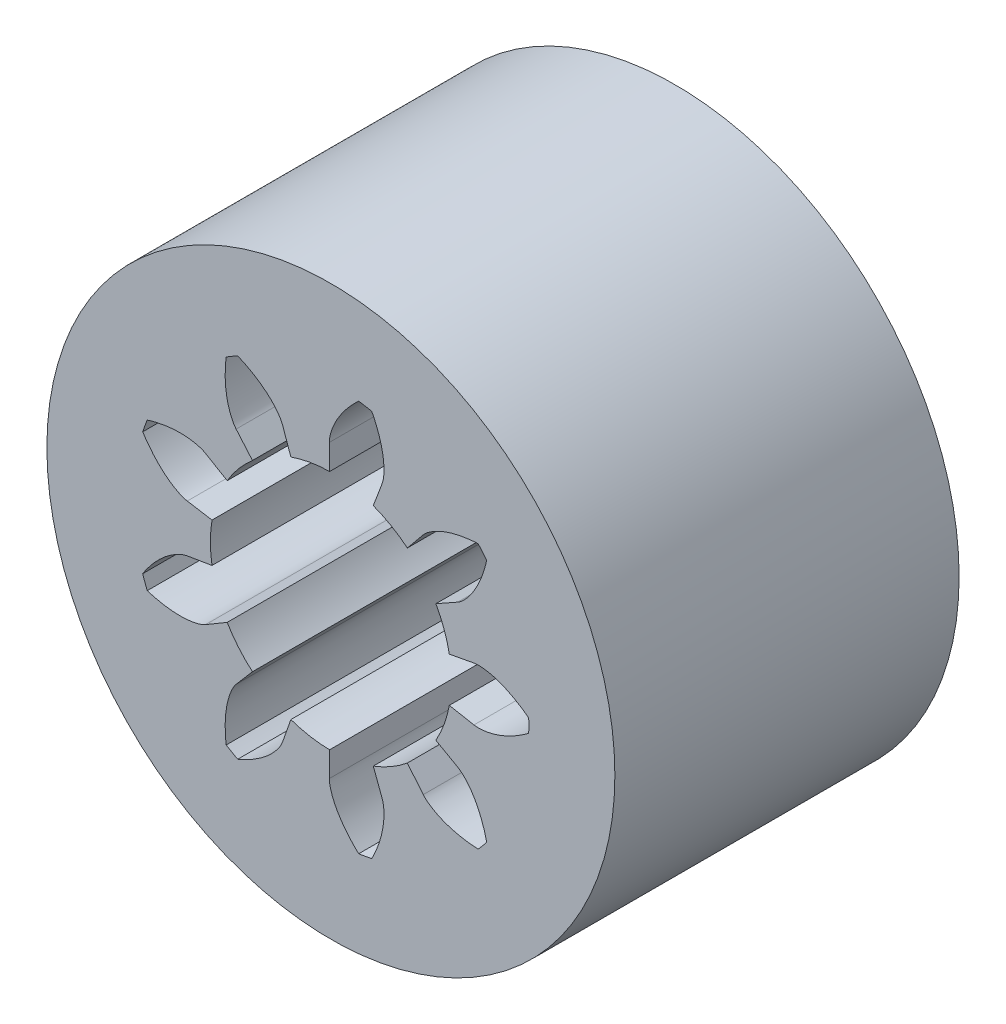
SolidWorks part; units mm, degrees
ref_plane "前视基准面" through (0, 0, 0) normal (0, 0, 1) x (1, 0, 0)
ref_plane "上视基准面" through (0, 0, 0) normal (0, 1, 0) x (1, 0, 0)
ref_plane "右视基准面" through (0, 0, 0) normal (1, 0, 0) x (0, 0, -1)
other "Configuration Table"
sketch "草图1" plane through (0, 0, 0) normal (0, 0, 1) x (1, 0, 0)
  line L0 (0, 0) -> (1.7727, 0.3126) construction
  line L1 (0, 0) -> (1.6625, 0.3114)
  line L2 (0, 0) -> (1.6625, -0.3114)
  line L3 (0, 0) -> (1.7727, -0.3126) construction
  line L4 (0, 0) -> (2.3, 0) construction
  line L5 (1.7727, 0.3126) -> (1.7727, -0.3126) construction
  circle A0 centre (0, 0) radius 1.4
  circle A1 centre (0, 0) radius 2.3
  circle A2 centre (0, 0) radius 1.6914 construction
  circle A3 centre (0, 0) radius 1.8 construction
  circle A4 centre (0, 0) radius 3.3
  spline S0 degree 4 poles (1.6625, 0.3114) (1.6752, 0.3138) (1.7111, 0.3177) (1.7802, 0.3144) (1.8904, 0.2938) (2.0276, 0.2452) (2.1931, 0.1584) (2.3697, 0.0286) (2.5413, -0.1401) (2.6992, -0.3458) (2.8304, -0.5693) (2.9355, -0.8061) (3.0193, -1.0647) (3.0889, -1.3941) (3.1213, -1.7947) (3.0901, -2.2611) (2.9766, -2.7674) (2.7903, -3.2521) (2.5424, -3.7067) (2.2354, -4.1264) (1.8851, -4.5047) (1.4847, -4.8415) (1.0641, -5.1287) (0.5898, -5.3747) (0.2176, -5.5283) (-0.215, -5.6619) (-0.4662, -5.7211) (-0.7551, -5.7803) (-0.9018, -5.796) (-1.0304, -5.8149) (-1.0698, -5.8173) (-1.0977, -5.8205) (-1.1128, -5.8223) knots 0 0 0 0 0 0.005604 0.015718 0.02996 0.048734 0.068727 0.096889 0.125051 0.153212 0.181374 0.209535 0.237696 0.271429 0.327752 0.384075 0.440398 0.496721 0.553044 0.609367 0.66569 0.722013 0.778336 0.834659 0.890982 0.909091 0.954545 0.977273 0.988636 0.994318 1 1 1 1 1 construction
  spline S1 degree 4 poles (1.6625, 0.3114) (1.6752, 0.3138) (1.7111, 0.3177) (1.7802, 0.3144) (1.8904, 0.2938) (2.0276, 0.2452) (2.1931, 0.1584) (2.3697, 0.0286) (2.5413, -0.1401) (2.6992, -0.3458) (2.8304, -0.5693) (2.9355, -0.8061) (3.0193, -1.0647) (3.0889, -1.3941) (3.1213, -1.7947) (3.0901, -2.2611) (2.9766, -2.7674) (2.7903, -3.2521) (2.5424, -3.7067) (2.2354, -4.1264) (1.8851, -4.5047) (1.4847, -4.8415) (1.0641, -5.1287) (0.5898, -5.3747) (0.2176, -5.5283) (-0.1034, -5.6274) (-0.2541, -5.668) (-0.2907, -5.6774) knots 0 0 0 0 0 0.005604 0.015718 0.02996 0.048734 0.068727 0.096889 0.125051 0.153212 0.181374 0.209535 0.237696 0.271429 0.327752 0.384075 0.440398 0.496721 0.553044 0.609367 0.66569 0.722013 0.778336 0.834659 0.890982 0.909091 0.909091 0.909091 0.909091 0.909091
  spline S2 degree 4 poles (1.6625, -0.3114) (1.6752, -0.3138) (1.7111, -0.3177) (1.7802, -0.3144) (1.8904, -0.2938) (2.0276, -0.2452) (2.1931, -0.1584) (2.3697, -0.0286) (2.5413, 0.1401) (2.6992, 0.3458) (2.8304, 0.5693) (2.9355, 0.8061) (3.0193, 1.0647) (3.0889, 1.3941) (3.1213, 1.7947) (3.0901, 2.2611) (2.9766, 2.7674) (2.7903, 3.2521) (2.5424, 3.7067) (2.2354, 4.1264) (1.8851, 4.5047) (1.4847, 4.8415) (1.0641, 5.1287) (0.5898, 5.3747) (0.2176, 5.5283) (-0.215, 5.6619) (-0.4662, 5.7211) (-0.7551, 5.7803) (-0.9018, 5.796) (-1.0304, 5.8149) (-1.0698, 5.8173) (-1.0977, 5.8205) (-1.1128, 5.8223) knots 0 0 0 0 0 0.005604 0.015718 0.02996 0.048734 0.068727 0.096889 0.125051 0.153212 0.181374 0.209535 0.237696 0.271429 0.327752 0.384075 0.440398 0.496721 0.553044 0.609367 0.66569 0.722013 0.778336 0.834659 0.890982 0.909091 0.954545 0.977273 0.988636 0.994318 1 1 1 1 1 construction
  spline S3 degree 4 poles (1.6625, -0.3114) (1.6752, -0.3138) (1.7111, -0.3177) (1.7802, -0.3144) (1.8904, -0.2938) (2.0276, -0.2452) (2.1931, -0.1584) (2.3697, -0.0286) (2.5413, 0.1401) (2.6992, 0.3458) (2.8304, 0.5693) (2.9355, 0.8061) (3.0193, 1.0647) (3.0889, 1.3941) (3.1213, 1.7947) (3.0901, 2.2611) (2.9766, 2.7674) (2.7903, 3.2521) (2.5424, 3.7067) (2.2354, 4.1264) (1.8851, 4.5047) (1.4847, 4.8415) (1.0641, 5.1287) (0.5898, 5.3747) (0.2176, 5.5283) (-0.1034, 5.6274) (-0.2541, 5.668) (-0.2907, 5.6774) knots 0 0 0 0 0 0.005604 0.015718 0.02996 0.048734 0.068727 0.096889 0.125051 0.153212 0.181374 0.209535 0.237696 0.271429 0.327752 0.384075 0.440398 0.496721 0.553044 0.609367 0.66569 0.722013 0.778336 0.834659 0.890982 0.909091 0.909091 0.909091 0.909091 0.909091
  point P16 (1.7727, 0)
  dimension "内啮合齿顶圆直径" = 2.8
  dimension "内啮合分度圆直径" = 3.6
  dimension "内啮合基圆直径" = 3.3829
  dimension "内啮合齿根圆直径" = 4.6
  dimension "外径" = 6.6
  dimension "渐开线镜像线夹角" = 10
extrude "凸台-拉伸1" add sketch "草图1" along normal blind 4 contours A4 | A0
extrude "切除-拉伸2" cut sketch "草图1<3>" along normal through all contours A0 S3 A1 S1 region at (1.7935, 0, 0)
sketch "草图1<3>" plane through (0, 0, 0) normal (0, 0, 1) x (1, 0, 0) same geometry as "草图1"
pattern_circular "阵列(圆周)1" count 9 over 360 about axis through (0, 0, 4) along (0, 0, 1) of "切除-拉伸2"
equation "\"m\"= 0.4'模数"
equation "\"z1\"= 17'外啮合齿轮数"
equation "\"a\"= 20度'压力角"
equation "\"z2\"= 9'内啮合齿轮数"
equation "\"hax\"= 1'齿顶高系数"
equation "\"cx\"= 0.25'顶隙系数"
equation "\"ha\"= \"hax\" * \"m\"'齿顶高"
equation "\"hf\"= ( \"hax\" + \"cx\" ) * \"m\"'齿根高"
equation "\"d1\"= \"m\" * \"z1\"'外啮合分度圆直径"
equation "\"da1\"= ( \"z1\" + 2 ) * \"m\"'外啮合齿顶圆直径"
equation "\"df1\"= \"d1\" - 2 * \"hf\"'外啮合齿根圆直径"
equation "\"db1\"= \"d1\" * cos ( \"a\" )'外啮合基圆直径"
equation "\"p\"= \"m\" * PI'齿距"
equation "\"d2\"= \"m\" * \"z2\"'内啮合分度圆直径"
equation "\"db2\"= \"d2\" * cos ( \"a\" )'内啮合基圆直径"
equation "\"da2\"= ( \"z2\" - 2 ) * \"m\"'内啮合齿顶圆直径"
equation "\"df2\"= \"d2\" + 2 * \"hf\"'内啮合齿根圆直径"
equation "\"内啮合齿顶圆直径@草图1\"= \"da2\""
equation "\"内啮合齿根圆直径@草图1\"= \"df2\""
equation "\"内啮合分度圆直径@草图1\"= \"d2\""
equation "\"内啮合基圆直径@草图1\"= \"db2\""
equation "\"渐开线镜像线夹角@草图1\"= 360度 / 4 / \"z2\""
equation "\"do\"= IIF ( \"edo\" >= ( \"df2\" + 2 ) , \"edo\" , ( \"df2\" + 2 ) )'外圈直径"
equation "\"h\"= 4'厚度"
equation "\"外径@草图1\"= \"do\""
equation "\"厚度@凸台-拉伸1\"= \"h\""
equation "\"内啮合齿轮数@阵列(圆周)1\"= \"z2\""
equation "\"edo\" = 5'期望的外圈直径"
